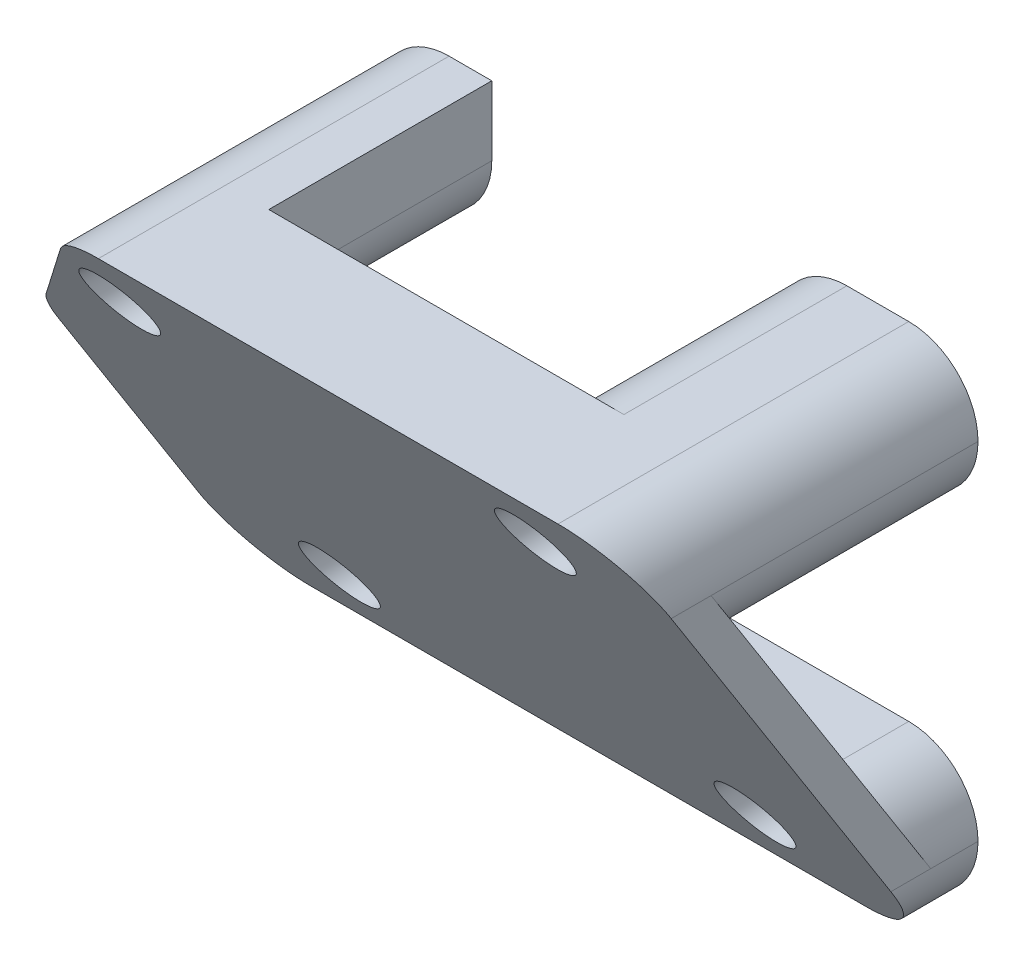
SolidWorks part; units mm, degrees
ref_plane "Front Plane" through (0, 0, 0) normal (0, 0, 1) x (1, 0, 0)
ref_plane "Top Plane" through (0, 0, 0) normal (0, 1, 0) x (1, 0, 0)
ref_plane "Right Plane" through (0, 0, 0) normal (1, 0, 0) x (0, 0, -1)
sketch "Sketch1" plane through (0, 0, 0) normal (1, 0, 0) x (0, 0, -1)
  line L0 (-6.4019, 19.3633) -> (12.0395, 19.3633)
  line L2 (9.3196, -5.4228) -> (-6.4019, 19.3633)
  line L3 (12.0395, -0.6367) -> (31.0682, -30.6367)
  line L5 (29.951, -37.9497) -> (9.3196, -5.4228)
  line L6 (12.0395, -0.6367) -> (12.0395, 19.3633)
  line L10 (29.951, -37.9497) -> (37.9982, -50.6367)
  line L11 (37.9982, -50.6367) -> (44.2357, -50.6367)
  line L12 (44.2357, -50.6367) -> (44.2357, -30.6367)
  line L13 (44.2357, -30.6367) -> (31.0682, -30.6367)
  point P5 (12.0395, 9.3633)
  point P8 (44.2357, -40.6367)
  dimension "D1" = 50
extrude "Boss-Extrude1" add sketch "Sketch1" along normal blind 100
sketch "Sketch2" plane through (0, 0, -44.2357) normal (0, 0, -1) x (-1, 0, 0)
  line L0 (-100, -0.6367) -> (-100, 19.3633) construction
  line L2 (0, -50.6367) -> (0, -30.6367) construction
  circle A0 centre (-80, -41.2364) radius 5
  circle A1 centre (-20, -41.2364) radius 5
  circle A2 centre (-20, 8.7636) radius 5
  circle A3 centre (-80, 8.7636) radius 5
  dimension "D1" = 60
  dimension "D2" = 50
  dimension "D3" = 60
  dimension "D4" = 20
  dimension "D5" = 20
extrude "Cut-Extrude1" cut sketch "Sketch2" against normal blind 61
fillet "Fillet1" radius 10 6 edges at (100, 19.3633, -2.8188) (0, 19.3633, -2.8188) (0, -30.6367, -37.6519) (0, -50.6367, -41.117) (100, -50.6367, -41.117) (100, -30.6367, -37.6519)
sketch "Sketch3" plane through (0, 0, -12.0395) normal (0, 0, -1) x (-1, 0, 0)
  line L0 (-18.6302, 19.3633) -> (0, -5.5424)
  line L1 (-90, 19.3633) -> (-10, 19.3633) construction
  line L2 (0, -5.5424) -> (0, 25.0266)
  line L3 (0, 25.0266) -> (-18.6302, 25.0266)
  line L4 (-18.6302, 25.0266) -> (-18.6302, 19.3633)
extrude "Cut-Extrude3" cut sketch "Sketch3" against normal blind 56 and the other way blind 56
fillet "Fillet2" radius 10 2 edges at (0, -5.5424, -12.2733) (18.6302, 19.3633, -2.8188)
sketch "Sketch4" plane through (0, 0, -12.0395) normal (0, 0, -1) x (-1, 0, 0)
  line L0 (-100, -0.6367) -> (-100, 9.3633)
  line L2 (-3.6696, -0.6367) -> (-15.6305, 15.3532)
  line L4 (-71.0702, 19.3633) -> (-71.0702, -0.6367)
  line L5 (-29.8024, -0.6367) -> (-3.6696, -0.6367)
  line L6 (-29.8024, -0.6367) -> (-29.8024, 19.3633)
  line L7 (-100, -0.6367) -> (-71.0702, -0.6367)
  line L8 (-90, 19.3633) -> (-71.0702, 19.3633)
  line L9 (-29.8024, 19.3633) -> (-23.6381, 19.3633)
  arc A0 (-100, 9.3633) -> (-90, 19.3633) centre (-90, 9.3633) cw
  arc A1 (-23.6381, 19.3633) -> (-15.6305, 15.3532) centre (-23.6381, 9.3633) cw
  circle A2 centre (-80, 8.7636) radius 5
  circle A3 centre (-20, 8.7636) radius 5
extrude "Boss-Extrude2" add sketch "Sketch4" along normal up to surface (32.1962 mm away) up to face at (20, -36.2364, -44.2357)
fillet "Fillet5" radius 10 4 edges at (71.0702, 19.3633, -28.1376) (100, -0.6367, -28.1376) (71.0702, -0.6367, -28.1376) (29.8024, -0.6367, -28.1376)
sketch "Sketch5" plane through (0, 5.263, -8.2974) normal (0, 0.5356, -0.8445) x (-1, 0, 0)
  line L0 (86.1517, 411.5493) -> (686.1517, 411.5493) construction
  line L1 (-61.8558, -19.4931) -> (-59.1064, -22.2402)
  line L2 (-59.1064, -22.2402) -> (-51.5172, -20.1861)
  line L3 (-51.5172, -20.1861) -> (-49.4879, -12.6136)
  line L4 (-49.4879, -12.6136) -> (-52.2373, -9.8665)
  line L5 (-52.2373, -9.8665) -> (-54.2511, -17.3808)
  line L6 (-54.2511, -17.3808) -> (-61.8558, -19.4931)
  line L7 (-60.4811, -30.5564) -> (-57.736, -33.2992)
  line L8 (-57.736, -33.2992) -> (-55.7254, -25.7967)
  line L9 (-55.7254, -25.7967) -> (-48.1327, -23.6877)
  line L10 (-48.1327, -23.6877) -> (-50.8626, -20.9602)
  line L11 (-50.8626, -20.9602) -> (-58.47, -23.0732)
  line L12 (-58.47, -23.0732) -> (-60.4811, -30.5564)
  line L13 (-45.3023, -16.7989) -> (-42.6058, -19.4931)
  line L14 (-42.6058, -19.4931) -> (-44.643, -27.0739)
  line L15 (-44.643, -27.0739) -> (-52.2373, -29.1833)
  line L16 (-52.2373, -29.1833) -> (-54.9389, -26.4841)
  line L17 (-54.9389, -26.4841) -> (-47.3919, -24.3878)
  line L18 (-47.3919, -24.3878) -> (-45.3023, -16.7989)
  text T0 "<b>Ingenuity </b>Labs"
extrude "Cut-Extrude4" cut sketch "Sketch5" against normal blind 0.2
